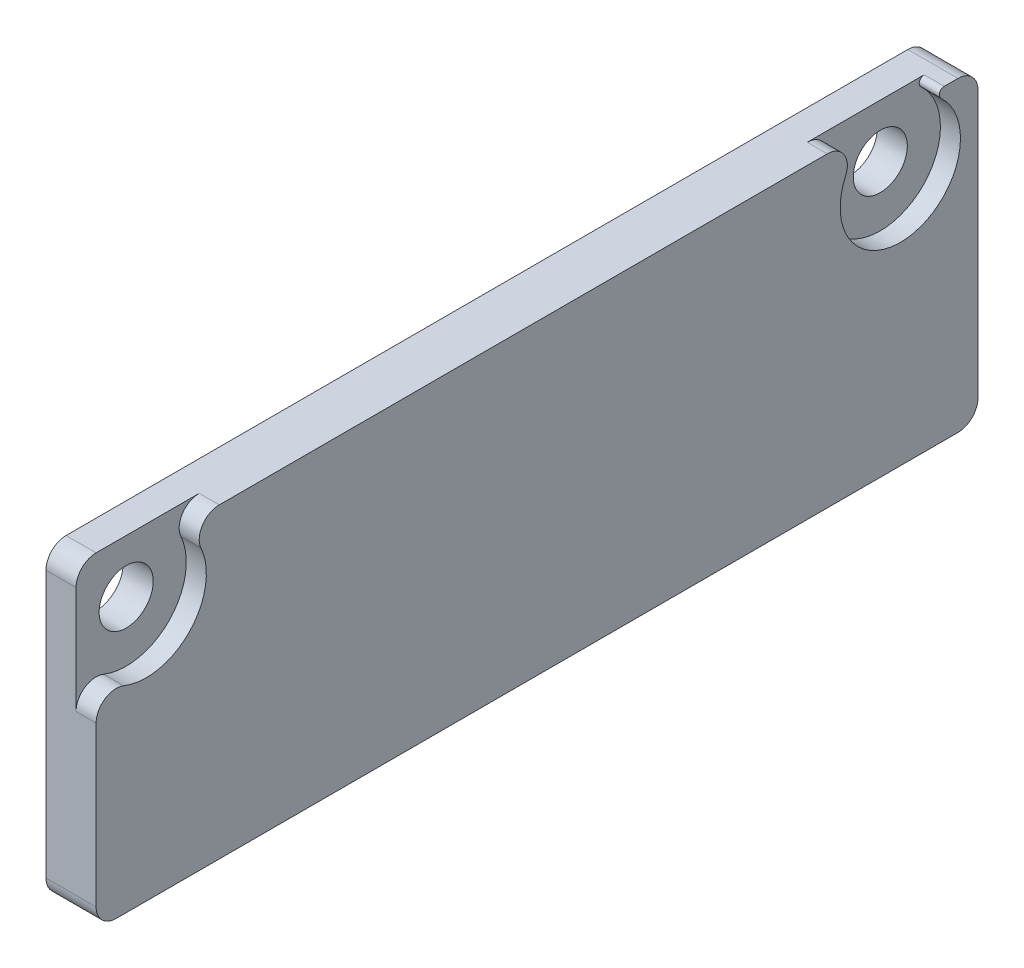
SolidWorks part; units mm, degrees
material "ABS"
ref_plane "Front Plane" through (0, 0, 0) normal (0, 0, 1) x (1, 0, 0)
ref_plane "Top Plane" through (0, 0, 0) normal (0, 1, 0) x (1, 0, 0)
ref_plane "Right Plane" through (0, 0, 0) normal (1, 0, 0) x (0, 0, -1)
sketch "Sketch1" plane through (0, 0, 0) normal (1, 0, 0) x (0, 0, -1)
  line L0 (-19.5, 5) -> (18.125, 5) construction
  line L1 (-22, -7.65) -> (22, -7.65)
  line L2 (-22, -7.65) -> (-22, 7.65)
  line L3 (-22, 7.65) -> (22, 7.65)
  line L4 (22, -7.65) -> (22, 7.65)
  line L5 (-22, -7.65) -> (22, 7.65) construction
  line L6 (-22, 7.65) -> (22, -7.65) construction
  point P0 (0, 0)
  dimension "D1" = 15.3
  dimension "D2" = 44
  dimension "D3" = 2.65
  dimension "D4" = 2.5
  dimension "D5" = 3.875
extrude "Boss-Extrude1" add sketch "Sketch1" along normal blind 2.5
sketch "Sketch3" plane through (2.5, 0, 0) normal (1, 0, 0) x (0, 0, -1)
  point P0 (-19.5, 5)
  point P3 (18.125, 5)
hole_wizard "CBORE for M2.5 Pan Head Machine Screw1" positions "Sketch3" profile "Sketch4" counterbore size "M2.5" standard "ANSI Metric" end condition through all
sketch "Sketch4" plane through (2.5, 5, 19.5) normal (0, 1, 0) x (0, 0, -1)
  line L0 (0, 0) -> (0, 2.5)
  line L1 (0, 2.5) -> (1.35, 2.5)
  line L3 (1.35, 2.5) -> (1.35, 1)
  line L4 (1.35, 1) -> (3, 1)
  line L5 (3, 1) -> (3, 0)
  line L7 (3, 0) -> (0, 0)
  line L11 (0, -6.35) -> (0, 107.95) construction
  dimension "Thru Hole Dia." = 2.7
  dimension "Thru Hole Depth" = 2.5
  dimension "C'Bore Dia." = 6
  dimension "C'Bore Depth" = 1
sketch "Sketch5" plane through (2.5, 0, 0) normal (1, 0, 0) x (0, 0, -1)
  line L2 (-22, 7.65) -> (-22, 6.6583)
  line L3 (-20.9062, 7.65) -> (-22, 7.65)
  line L4 (-22, 7.65) -> (-22, 6.6583)
  line L5 (-20.9062, 7.65) -> (-22, 7.65)
  line L6 (-22, 7.65) -> (-22, 6.6583)
  line L7 (-22, 7.65) -> (-22, 6.6583)
  line L10 (-20.9062, 7.65) -> (-22, 7.65)
  line L11 (-20.9062, 7.65) -> (-22, 7.65)
  arc A1 (-20.9062, 7.65) -> (-22, 6.6583) centre (-19.5, 5) ccw
  arc A2 (-20.9062, 7.65) -> (-22, 6.6583) centre (-19.5, 5) ccw
  arc A3 (-20.9062, 7.65) -> (-22, 6.6583) centre (-19.5, 5) ccw
  arc A5 (-20.9062, 7.65) -> (-22, 6.6583) centre (-19.5, 5) ccw
  dimension "D1" = 0
  dimension "D2" = 0
extrude "Cut-Extrude1" cut sketch "Sketch5" against normal up to surface (1 mm away) contours A2 L5 L4 region at (2.5, 7.3473, 21.6672) up to face at (1.5, 5, 18.15)
fillet "Fillet1" radius 1 7 edges at (2, 7.65, -16.7188) (2, 3.3417, 22) (2, 7.65, 18.0938) (0.75, 7.65, 22) (1.25, 7.65, -22) (1.25, -7.65, -22) (1.25, -7.65, 22)
fillet "Fillet2" radius 0.25 1 edges at (2, 7.65, -19.5312)
